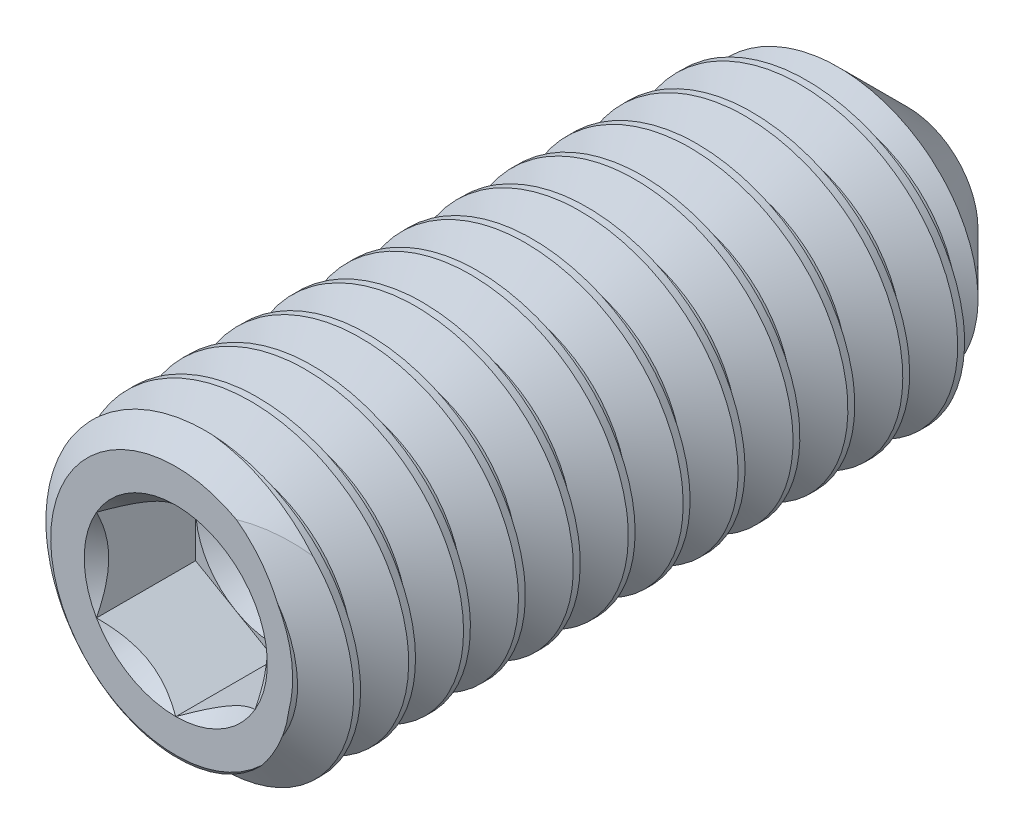
SolidWorks part; units mm, degrees
other "Imported1" parameters "D3"=6.6, "D1"=46.842, "Length"=6, "Drive Size"=1.3, "Thread Size"=2.5, "Thread Pitch"=0.45, "D2"=0.0866, "hex Depth"=0.8125, "Dia"=12, "D4"=2.3829, "Cup Point Dia"=3.3528, "D5"=1.436, "D6"=1.4986, "D7"=5.0014, "Pitch"=1.75
ref_plane "Front" through (0, 0, 0) normal (0, 0, 1) x (1, 0, 0)
ref_plane "Top" through (0, 0, 0) normal (0, 1, 0) x (1, 0, 0)
ref_plane "Right" through (0, 0, 0) normal (1, 0, 0) x (0, 0, -1)
sketch "Sketch1" plane through (0, 0, 0) normal (1, 0, 0) x (0, 0, -1)
  line L0 (3, 1.25) -> (-3, 1.25) construction
  line L1 (-3, 1.25) -> (-3, -1.25) construction
  line L2 (-3, -1.25) -> (3, -1.25) construction
  line L3 (3, -1.25) -> (3, 1.25) construction
  line L4 (-3, 0.65) -> (-3, -0.65) construction
  line L5 (2.9719, 1.2987) -> (3.4219, 1.2987) construction
  line L6 (2.9719, 1.2987) -> (3, 1.25) construction
  line L7 (3, 1.25) -> (3.3938, 1.25) construction
  line L8 (3.3938, 1.25) -> (3.4219, 1.2987) construction
  line L9 (3, 1.25) -> (3.1969, 0.909) construction
  line L10 (3.1969, 0.909) -> (3.3938, 1.25) construction
  line L11 (3.1688, 0.9577) -> (3.225, 0.9577) construction
  line L12 (3.1969, 1.2987) -> (3.1969, 1.25) construction
  line L13 (3.1969, 0.9577) -> (3.1969, 0.909) construction
  point P3 (0, 1.25)
  point P24 (-3, 0)
  point P25 (-3, 0)
  dimension "D1" = 0.0563
sketch "Sketch11" plane through (0, 0, 0) normal (1, 0, 0) x (0, 0, -1)
  line L0 (-3, 0) -> (-3, 1.025)
  line L1 (-3, 1.025) -> (-2.8425, 1.25)
  line L2 (-2.8425, 1.25) -> (2.325, 1.25)
  line L3 (2.325, 1.25) -> (3, 0.575)
  line L4 (3, 0.575) -> (2.6545, 0)
  line L5 (2.6545, 0) -> (-3, 0)
  line L6 (2.6545, 0) -> (3, 0) construction
  line L7 (3, 0) -> (3, 0.575) construction
  line L8 (3, -0.575) -> (2.6545, 0) construction
  line L9 (-2.8425, -1.25) -> (2.325, -1.25) construction
  line L10 (-3, -1.25) -> (3, -1.25) construction
  line L11 (-3, 1.25) -> (-3, -1.25) construction
  line L12 (3, -1.25) -> (3, 1.25) construction
  point P11 (1.425, -1.25)
  point P12 (-3, 1.25)
  dimension "D3" = 35
  dimension "D5" = 118
  dimension "D6" = 45
  dimension "D1" = 0.225
  dimension "D2" = 1.575
  dimension "D4" = 0.675
revolve "Revolve1" add sketch "Sketch11" angle 360 about L6
sketch "Sketch2" plane through (0, 0, 3) normal (0, 0, 1) x (1, 0, 0)
  line L1 (0, 0.7506) -> (-0.65, 0.3753)
  line L2 (-0.65, 0.3753) -> (-0.65, -0.3753)
  line L3 (-0.65, -0.3753) -> (0, -0.7506)
  line L4 (0, -0.7506) -> (0.65, -0.3753)
  line L5 (0.65, -0.3753) -> (0.65, 0.3753)
  line L6 (0.65, 0.3753) -> (0, 0.7506)
  circle A0 centre (0, 0) radius 0.65 construction
  circle A1 centre (0, 0) radius 1.25 construction
extrude "Cut-Extrude1" cut sketch "Sketch2" against normal blind 0.8125
sketch "Sketch3" plane through (0, 0, 3) normal (0, 0, 1) x (1, 0, 0)
  circle A0 centre (0, 0) radius 0.7506
extrude "Cut-Extrude2" cut sketch "Sketch3" against normal through all draft 45
sketch "Sketch4" plane through (0, 0, 2.1875) normal (0, 0, 1) x (1, 0, 0)
  circle A0 centre (0, 0) radius 0.65 construction
  circle A1 centre (0, 0) radius 0.65
extrude "Cut-Extrude3" cut sketch "Sketch4" against normal through all draft 60
sketch "Sketch13" plane through (0, 0, 0) normal (1, 0, 0) x (0, 0, -1)
  line L0 (0, -1.25) -> (0, 1.25) construction
  line L2 (-2.8425, 1.25) -> (2.325, 1.25) construction
  line L4 (2.6545, 0) -> (-3, 0) construction
  point P0 (0.1545, 0)
  point P4 (0, 0)
  point P9 (-0.1545, 0)
  dimension "D1" = 2.5
ref_plane "Plane1" through (0, 0, -3) normal (0, 0, 1) x (1, 0, 0)
sketch "Sketch5" plane through (0, 0, -3) normal (0, 0, 1) x (1, 0, 0)
  circle A0 centre (0, 0) radius 1.25 construction
  circle A1 centre (0, 0) radius 1.25
curve "Helix/Spiral1" pitch 0.45 height 6.6 radius 1.25 centre (0, 0, -3) axis (0, 0, 1) start towards (0, 1, 0)
sketch "Sketch6" plane through (0, 0, 0) normal (1, 0, 0) x (0, 0, -1)
  line L0 (2.9859, 1.2744) -> (3.4078, 1.2744)
  line L1 (2.9719, 1.2987) -> (3, 1.25) construction
  line L2 (3.3938, 1.25) -> (3.4219, 1.2987) construction
  line L3 (3.4078, 1.2744) -> (3.225, 0.9577)
  line L4 (3.225, 0.9577) -> (3.1688, 0.9577)
  line L5 (3.1688, 0.9577) -> (2.9859, 1.2744)
sweep "Cut-Sweep1" cut profiles "Sketch6" path "Helix/Spiral1"
equation "\"D3@Helix/Spiral1\" = \"Length@Sketch1\" * 1.1"
equation "\"hex Depth@Cut-Extrude1\"=\"Drive Size@Sketch1\" * .625"
equation "\"D1@Sketch11\" = \"Thread Pitch@Sketch1\" * .5"
equation "\"D2@Sketch11\" = \"Thread Pitch@Sketch1\" * 3.5"
equation "\"D1@Helix/Spiral1\" = \"Thread Pitch@Sketch1\""
equation "\"D4@Sketch11\" = \"Thread Pitch@Sketch1\" * 1.5"
equation "\"D1@Sketch1\" = \"Thread Pitch@Sketch1\" / 8"
equation "\"D1@Sketch13\"=\"Thread Size@Sketch1\""
